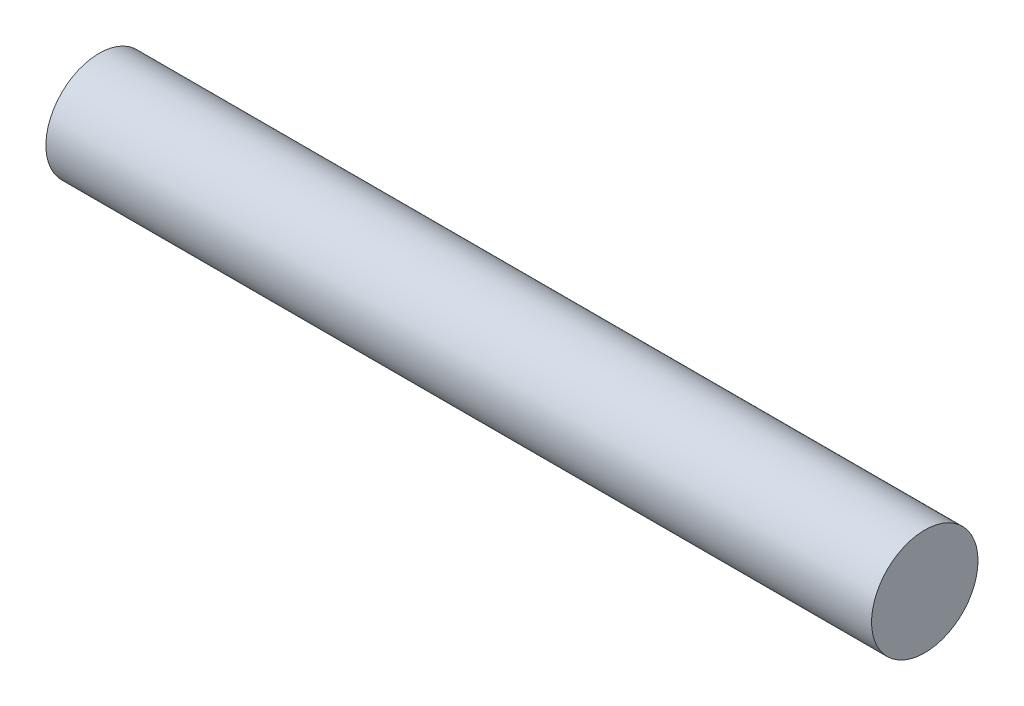
SolidWorks part; units mm, degrees
ref_plane "Front Plane" through (0, 0, 0) normal (0, 0, 1) x (1, 0, 0)
ref_plane "Top Plane" through (0, 0, 0) normal (0, 1, 0) x (1, 0, 0)
ref_plane "Right Plane" through (0, 0, 0) normal (1, 0, 0) x (0, 0, -1)
sketch "Sketch2" plane through (0, 0, 0) normal (1, 0, 0) x (0, 0, -1)
  circle A0 centre (0, 0) radius 0.685
  dimension "D1" = 1.37
extrude "Boss-Extrude1" add sketch "Sketch2" along normal blind 5.315 and the other way blind 5.315
